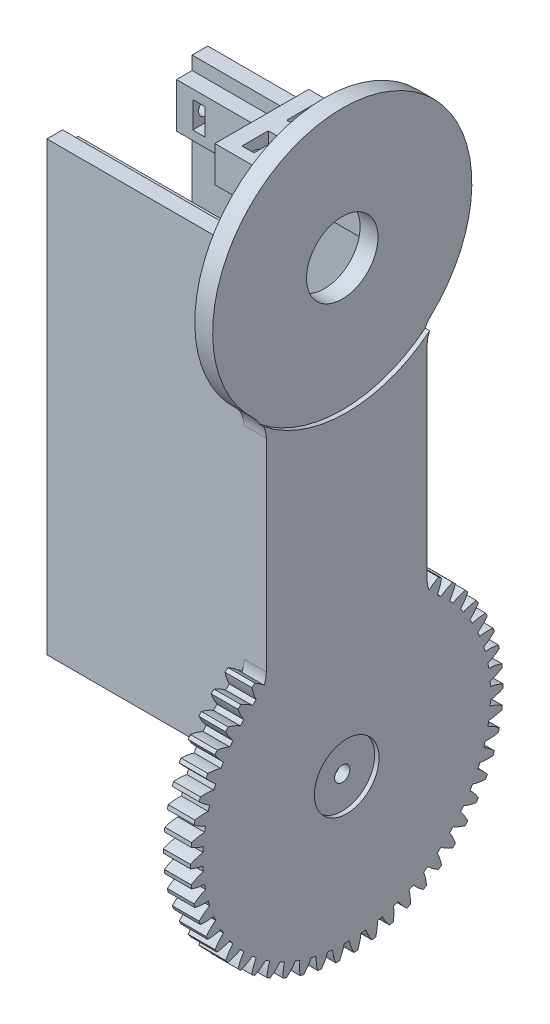
SolidWorks part; units mm, degrees
ref_plane "Front Plane" through (0, 0, 0) normal (0, 0, 1) x (1, 0, 0)
ref_plane "Top Plane" through (0, 0, 0) normal (0, 1, 0) x (1, 0, 0)
ref_plane "Right Plane" through (0, 0, 0) normal (1, 0, 0) x (0, 0, -1)
sketch "Sketch1" plane through (0, 0, 0) normal (1, 0, 0) x (0, 0, -1)
  line L0 (-32, 131.6872) -> (-32, 177.0245)
  line L1 (4, 177.0245) -> (4, 131.6872)
  arc A0 (6.1892, 127.0528) -> (-34.1892, 127.0528) centre (-14, 102.5) cw
  arc A1 (-34.1892, 127.0528) -> (-32, 131.6872) centre (-38, 131.6872) ccw
  arc A2 (-32, 177.0245) -> (-33.8857, 181.3917) centre (-38, 177.0245) ccw
  arc A3 (-33.8857, 181.3917) -> (5.8857, 181.3917) centre (-14, 202.5) cw
  arc A4 (5.8857, 181.3917) -> (4, 177.0245) centre (10, 177.0245) ccw
  arc A5 (4, 131.6872) -> (6.1892, 127.0528) centre (10, 131.6872) ccw
  circle A6 centre (-14, 202.5) radius 8
extrude "Plate A" add sketch "Sketch1" along normal blind 5 from offset 22.05
sketch "Sketch2" plane through (0, 0, 0) normal (1, 0, 0) x (0, 0, -1)
  arc A0 (20.9973, 102.0644) -> (20.9973, 102.9356) centre (-14, 102.5) ccw
  arc A1 (18.1607, 103.8131) -> (18.0957, 104.9294) centre (-14, 102.5) ccw
  arc A2 (20.8112, 106.1303) -> (20.7101, 106.9956) centre (-14, 102.5) ccw
  arc A3 (17.7908, 107.5378) -> (17.5966, 108.6391) centre (-14, 102.5) ccw
  arc A4 (20.1544, 110.1471) -> (19.9535, 110.9948) centre (-14, 102.5) ccw
  arc A5 (16.991, 111.1945) -> (16.6703, 112.2657) centre (-14, 102.5) ccw
  arc A6 (19.0357, 114.0605) -> (18.7377, 114.8791) centre (-14, 102.5) ccw
  arc A7 (15.7721, 114.7335) -> (15.3292, 115.7603) centre (-14, 102.5) ccw
  arc A8 (17.4702, 117.8175) -> (17.0792, 118.596) centre (-14, 102.5) ccw
  arc A9 (14.1505, 118.1071) -> (13.5914, 119.0755) centre (-14, 102.5) ccw
  arc A10 (15.4792, 121.3674) -> (15.0004, 122.0953) centre (-14, 102.5) ccw
  arc A11 (12.1483, 121.2697) -> (11.4806, 122.1666) centre (-14, 102.5) ccw
  arc A12 (13.0895, 124.6621) -> (12.5295, 125.3295) centre (-14, 102.5) ccw
  arc A13 (9.7925, 124.1784) -> (9.0251, 124.9917) centre (-14, 102.5) ccw
  arc A14 (10.3334, 127.6572) -> (9.6998, 128.255) centre (-14, 102.5) ccw
  arc A15 (7.1149, 126.794) -> (6.2583, 127.5127) centre (-14, 102.5) ccw
  arc A16 (7.2483, 130.312) -> (6.5495, 130.8323) centre (-14, 102.5) ccw
  arc A17 (4.1518, 129.081) -> (3.2175, 129.6954) centre (-14, 102.5) ccw
  arc A18 (3.8759, 132.5907) -> (3.1214, 133.0263) centre (-14, 102.5) ccw
  arc A19 (0.9432, 131.0085) -> (-0.0561, 131.5104) centre (-14, 102.5) ccw
  arc A20 (0.2617, 134.4625) -> (-0.5383, 134.8076) centre (-14, 102.5) ccw
  arc A21 (-2.4675, 132.5506) -> (-3.5183, 132.933) centre (-14, 102.5) ccw
  arc A22 (-3.5454, 135.9021) -> (-4.38, 136.152) centre (-14, 102.5) ccw
  arc A23 (-6.0341, 133.6862) -> (-7.1222, 133.9441) centre (-14, 102.5) ccw
  arc A24 (-7.4938, 136.89) -> (-8.3518, 137.0412) centre (-14, 102.5) ccw
  arc A25 (-9.7085, 134.4001) -> (-10.8191, 134.5299) centre (-14, 102.5) ccw
  arc A26 (-11.5302, 137.4128) -> (-12.3999, 137.4634) centre (-14, 102.5) ccw
  arc A27 (-13.4409, 134.6826) -> (-14.5591, 134.6826) centre (-14, 102.5) ccw
  arc A28 (-15.6001, 137.4634) -> (-16.4698, 137.4128) centre (-14, 102.5) ccw
  arc A29 (-17.1809, 134.5299) -> (-18.2915, 134.4001) centre (-14, 102.5) ccw
  arc A30 (-19.6482, 137.0412) -> (-20.5062, 136.89) centre (-14, 102.5) ccw
  arc A31 (-20.8778, 133.9441) -> (-21.9659, 133.6862) centre (-14, 102.5) ccw
  arc A32 (-23.62, 136.152) -> (-24.4546, 135.9021) centre (-14, 102.5) ccw
  arc A33 (-24.4817, 132.933) -> (-25.5325, 132.5506) centre (-14, 102.5) ccw
  arc A34 (-27.4617, 134.8076) -> (-28.2617, 134.4625) centre (-14, 102.5) ccw
  arc A35 (-27.9439, 131.5104) -> (-28.9432, 131.0085) centre (-14, 102.5) ccw
  arc A36 (-31.1214, 133.0263) -> (-31.8759, 132.5907) centre (-14, 102.5) ccw
  arc A37 (-31.2175, 129.6954) -> (-32.1518, 129.081) centre (-14, 102.5) ccw
  arc A38 (-34.5495, 130.8323) -> (-35.2483, 130.312) centre (-14, 102.5) ccw
  arc A39 (-34.2583, 127.5127) -> (-35.1149, 126.794) centre (-14, 102.5) ccw
  arc A40 (-37.6998, 128.255) -> (-38.3334, 127.6572) centre (-14, 102.5) ccw
  arc A41 (-37.0251, 124.9917) -> (-37.7925, 124.1784) centre (-14, 102.5) ccw
  arc A42 (-40.5295, 125.3295) -> (-41.0895, 124.6621) centre (-14, 102.5) ccw
  arc A43 (-39.4806, 122.1666) -> (-40.1483, 121.2697) centre (-14, 102.5) ccw
  arc A44 (-43.0004, 122.0953) -> (-43.4792, 121.3674) centre (-14, 102.5) ccw
  arc A45 (-41.5914, 119.0755) -> (-42.1505, 118.1071) centre (-14, 102.5) ccw
  arc A46 (-45.0792, 118.596) -> (-45.4702, 117.8175) centre (-14, 102.5) ccw
  arc A47 (-43.3292, 115.7603) -> (-43.7721, 114.7335) centre (-14, 102.5) ccw
  arc A48 (-46.7377, 114.8791) -> (-47.0357, 114.0605) centre (-14, 102.5) ccw
  arc A49 (-44.6703, 112.2657) -> (-44.991, 111.1945) centre (-14, 102.5) ccw
  arc A50 (-47.9535, 110.9948) -> (-48.1544, 110.1471) centre (-14, 102.5) ccw
  arc A51 (-45.5966, 108.6391) -> (-45.7908, 107.5378) centre (-14, 102.5) ccw
  arc A52 (-48.7101, 106.9956) -> (-48.8112, 106.1303) centre (-14, 102.5) ccw
  arc A53 (-46.0957, 104.9294) -> (-46.1607, 103.8131) centre (-14, 102.5) ccw
  arc A54 (-48.9973, 102.9356) -> (-48.9973, 102.0644) centre (-14, 102.5) ccw
  arc A55 (-46.1607, 101.1869) -> (-46.0957, 100.0706) centre (-14, 102.5) ccw
  arc A56 (-48.8112, 98.8697) -> (-48.7101, 98.0044) centre (-14, 102.5) ccw
  arc A57 (-45.7908, 97.4622) -> (-45.5966, 96.3609) centre (-14, 102.5) ccw
  arc A58 (-48.1544, 94.8529) -> (-47.9535, 94.0052) centre (-14, 102.5) ccw
  arc A59 (-44.991, 93.8055) -> (-44.6703, 92.7343) centre (-14, 102.5) ccw
  arc A60 (-47.0357, 90.9395) -> (-46.7377, 90.1209) centre (-14, 102.5) ccw
  arc A61 (-43.7721, 90.2665) -> (-43.3292, 89.2397) centre (-14, 102.5) ccw
  arc A62 (-45.4702, 87.1825) -> (-45.0792, 86.404) centre (-14, 102.5) ccw
  arc A63 (-42.1505, 86.8929) -> (-41.5914, 85.9245) centre (-14, 102.5) ccw
  arc A64 (-43.4792, 83.6326) -> (-43.0004, 82.9047) centre (-14, 102.5) ccw
  arc A65 (-40.1483, 83.7303) -> (-39.4806, 82.8334) centre (-14, 102.5) ccw
  arc A66 (-41.0895, 80.3379) -> (-40.5295, 79.6705) centre (-14, 102.5) ccw
  arc A67 (-37.7925, 80.8216) -> (-37.0251, 80.0083) centre (-14, 102.5) ccw
  arc A68 (-38.3334, 77.3428) -> (-37.6998, 76.745) centre (-14, 102.5) ccw
  arc A69 (-35.1149, 78.206) -> (-34.2583, 77.4873) centre (-14, 102.5) ccw
  arc A70 (-35.2483, 74.688) -> (-34.5495, 74.1677) centre (-14, 102.5) ccw
  arc A71 (-32.1518, 75.919) -> (-31.2175, 75.3046) centre (-14, 102.5) ccw
  arc A72 (-31.8759, 72.4093) -> (-31.1214, 71.9737) centre (-14, 102.5) ccw
  arc A73 (-28.9432, 73.9915) -> (-27.9439, 73.4896) centre (-14, 102.5) ccw
  arc A74 (-28.2617, 70.5375) -> (-27.4617, 70.1924) centre (-14, 102.5) ccw
  arc A75 (-25.5325, 72.4494) -> (-24.4817, 72.067) centre (-14, 102.5) ccw
  arc A76 (-24.4546, 69.0979) -> (-23.62, 68.848) centre (-14, 102.5) ccw
  arc A77 (-21.9659, 71.3138) -> (-20.8778, 71.0559) centre (-14, 102.5) ccw
  arc A78 (-20.5062, 68.11) -> (-19.6482, 67.9588) centre (-14, 102.5) ccw
  arc A79 (-18.2915, 70.5999) -> (-17.1809, 70.4701) centre (-14, 102.5) ccw
  arc A80 (-16.4698, 67.5872) -> (-15.6001, 67.5366) centre (-14, 102.5) ccw
  arc A81 (-14.5591, 70.3174) -> (-13.4409, 70.3174) centre (-14, 102.5) ccw
  arc A82 (-12.3999, 67.5366) -> (-11.5302, 67.5872) centre (-14, 102.5) ccw
  arc A83 (-10.8191, 70.4701) -> (-9.7085, 70.5999) centre (-14, 102.5) ccw
  arc A84 (-8.3518, 67.9588) -> (-7.4938, 68.11) centre (-14, 102.5) ccw
  arc A85 (-7.1222, 71.0559) -> (-6.0341, 71.3138) centre (-14, 102.5) ccw
  arc A86 (-4.38, 68.848) -> (-3.5454, 69.0979) centre (-14, 102.5) ccw
  arc A87 (-3.5183, 72.067) -> (-2.4675, 72.4494) centre (-14, 102.5) ccw
  arc A88 (-0.5383, 70.1924) -> (0.2617, 70.5375) centre (-14, 102.5) ccw
  arc A89 (-0.0561, 73.4896) -> (0.9432, 73.9915) centre (-14, 102.5) ccw
  arc A90 (3.1214, 71.9737) -> (3.8759, 72.4093) centre (-14, 102.5) ccw
  arc A91 (3.2175, 75.3046) -> (4.1518, 75.919) centre (-14, 102.5) ccw
  arc A92 (6.5495, 74.1677) -> (7.2483, 74.688) centre (-14, 102.5) ccw
  arc A93 (6.2583, 77.4873) -> (7.1149, 78.206) centre (-14, 102.5) ccw
  arc A94 (9.6998, 76.745) -> (10.3334, 77.3428) centre (-14, 102.5) ccw
  arc A95 (9.0251, 80.0083) -> (9.7925, 80.8216) centre (-14, 102.5) ccw
  arc A96 (12.5295, 79.6705) -> (13.0895, 80.3379) centre (-14, 102.5) ccw
  arc A97 (11.4806, 82.8334) -> (12.1483, 83.7303) centre (-14, 102.5) ccw
  arc A98 (15.0004, 82.9047) -> (15.4792, 83.6326) centre (-14, 102.5) ccw
  arc A99 (13.5914, 85.9245) -> (14.1505, 86.8929) centre (-14, 102.5) ccw
  arc A100 (17.0792, 86.404) -> (17.4702, 87.1825) centre (-14, 102.5) ccw
  arc A101 (15.3292, 89.2397) -> (15.7721, 90.2665) centre (-14, 102.5) ccw
  arc A102 (18.7377, 90.1209) -> (19.0357, 90.9395) centre (-14, 102.5) ccw
  arc A103 (16.6703, 92.7343) -> (16.991, 93.8055) centre (-14, 102.5) ccw
  arc A104 (19.9535, 94.0052) -> (20.1544, 94.8529) centre (-14, 102.5) ccw
  arc A105 (17.5966, 96.3609) -> (17.7908, 97.4622) centre (-14, 102.5) ccw
  arc A106 (20.7101, 98.0044) -> (20.8112, 98.8697) centre (-14, 102.5) ccw
  arc A107 (18.0957, 100.0706) -> (18.1607, 101.1869) centre (-14, 102.5) ccw
  spline S0 degree 3 poles (18.1607, 101.1869) (18.3503, 101.2175) (18.7327, 101.2791) (19.3001, 101.4275) (19.868, 101.6076) (20.4361, 101.819) (20.8092, 101.9822) (20.9973, 102.0644) knots 0 0 0 0 0.193275 0.389922 0.589928 0.793288 1 1 1 1
  spline S1 degree 3 poles (20.9973, 102.9356) (20.8092, 103.0178) (20.4361, 103.181) (19.868, 103.3924) (19.3001, 103.5725) (18.7327, 103.7209) (18.3503, 103.7825) (18.1607, 103.8131) knots 0 0 0 0 0.206712 0.410072 0.610078 0.806725 1 1 1 1
  spline S2 degree 3 poles (18.0957, 104.9294) (18.2804, 104.9818) (18.6531, 105.0874) (19.1994, 105.3007) (19.7426, 105.5455) (20.2823, 105.8214) (20.634, 106.0268) (20.8112, 106.1303) knots 0 0 0 0 0.193275 0.389922 0.589928 0.793288 1 1 1 1
  spline S3 degree 3 poles (20.7101, 106.9956) (20.5137, 107.0554) (20.1242, 107.1742) (19.5354, 107.3182) (18.9504, 107.4311) (18.3696, 107.5127) (17.9826, 107.5295) (17.7908, 107.5378) knots 0 0 0 0 0.206712 0.410072 0.610078 0.806725 1 1 1 1
  spline S4 degree 3 poles (17.5966, 108.6391) (17.774, 108.7125) (18.1319, 108.8607) (18.6498, 109.136) (19.1609, 109.4422) (19.6649, 109.7789) (19.9904, 110.0237) (20.1544, 110.1471) knots 0 0 0 0 0.193275 0.389922 0.589928 0.793288 1 1 1 1
  spline S5 degree 3 poles (19.9535, 110.9948) (19.7515, 111.0314) (19.3508, 111.1042) (18.7493, 111.1788) (18.1551, 111.2231) (17.5688, 111.2366) (17.1825, 111.2084) (16.991, 111.1945) knots 0 0 0 0 0.206712 0.410072 0.610078 0.806725 1 1 1 1
  spline S6 degree 3 poles (16.6703, 112.2657) (16.838, 112.3592) (17.1762, 112.548) (17.6586, 112.8815) (18.1308, 113.245) (18.5923, 113.6379) (18.8871, 113.9188) (19.0357, 114.0605) knots 0 0 0 0 0.193275 0.389922 0.589928 0.793288 1 1 1 1
  spline S7 degree 3 poles (18.7377, 114.8791) (18.5328, 114.8921) (18.1264, 114.9178) (17.5203, 114.9221) (16.925, 114.8971) (16.3411, 114.8425) (15.9606, 114.7696) (15.7721, 114.7335) knots 0 0 0 0 0.206712 0.410072 0.610078 0.806725 1 1 1 1
  spline S8 degree 3 poles (15.3292, 115.7603) (15.4848, 115.8727) (15.7989, 116.0994) (16.2394, 116.4866) (16.6661, 116.9025) (17.0789, 117.3463) (17.3391, 117.6596) (17.4702, 117.8175) knots 0 0 0 0 0.193275 0.389922 0.589928 0.793288 1 1 1 1
  spline S9 degree 3 poles (17.0792, 118.596) (16.8742, 118.5851) (16.4676, 118.5635) (15.8651, 118.4974) (15.2767, 118.4034) (14.7031, 118.2814) (14.3336, 118.1649) (14.1505, 118.1071) knots 0 0 0 0 0.206712 0.410072 0.610078 0.806725 1 1 1 1
  spline S10 degree 3 poles (13.5914, 119.0755) (13.733, 119.2052) (14.0186, 119.4669) (14.4111, 119.9026) (14.7867, 120.3652) (15.1452, 120.854) (15.3672, 121.1953) (15.4792, 121.3674) knots 0 0 0 0 0.193275 0.389922 0.589928 0.793288 1 1 1 1
  spline S11 degree 3 poles (15.0004, 122.0953) (14.7981, 122.0606) (14.3967, 121.9919) (13.806, 121.8564) (13.2325, 121.6947) (12.6769, 121.5069) (12.3235, 121.3483) (12.1483, 121.2697) knots 0 0 0 0 0.206712 0.410072 0.610078 0.806725 1 1 1 1
  spline S12 degree 3 poles (11.4806, 122.1666) (11.6061, 122.3119) (11.8594, 122.6049) (12.1987, 123.0833) (12.518, 123.5864) (12.8173, 124.1134) (12.9983, 124.4782) (13.0895, 124.6621) knots 0 0 0 0 0.193275 0.389922 0.589928 0.793288 1 1 1 1
  spline S13 degree 3 poles (12.5295, 125.3295) (12.3325, 125.2716) (11.9419, 125.1568) (11.3708, 124.9536) (10.82, 124.7264) (10.2899, 124.4754) (9.9573, 124.2768) (9.7925, 124.1784) knots 0 0 0 0 0.206712 0.410072 0.610078 0.806725 1 1 1 1
  spline S14 degree 3 poles (9.0251, 124.9917) (9.133, 125.1506) (9.3506, 125.4711) (9.632, 125.9856) (9.8908, 126.5223) (10.1268, 127.0806) (10.2642, 127.4639) (10.3334, 127.6572) knots 0 0 0 0 0.193275 0.389922 0.589928 0.793288 1 1 1 1
  spline S15 degree 3 poles (9.6998, 128.255) (9.5109, 128.1747) (9.1361, 128.0153) (8.5926, 127.7471) (8.0718, 127.4576) (7.5745, 127.1467) (7.2672, 126.9109) (7.1149, 126.794) knots 0 0 0 0 0.206712 0.410072 0.610078 0.806725 1 1 1 1
  spline S16 degree 3 poles (6.2583, 127.5127) (6.347, 127.683) (6.5259, 128.0266) (6.7457, 128.5703) (6.9404, 129.1334) (7.1101, 129.7153) (7.202, 130.112) (7.2483, 130.312) knots 0 0 0 0 0.193275 0.389922 0.589928 0.793288 1 1 1 1
  spline S17 degree 3 poles (6.5495, 130.8323) (6.3712, 130.7305) (6.0176, 130.5287) (5.5088, 130.1992) (5.0252, 129.8512) (4.5673, 129.4847) (4.2895, 129.2148) (4.1518, 129.081) knots 0 0 0 0 0.206712 0.410072 0.610078 0.806725 1 1 1 1
  spline S18 degree 3 poles (3.2175, 129.6954) (3.2858, 129.8749) (3.4237, 130.2369) (3.5788, 130.8025) (3.7069, 131.3844) (3.8078, 131.982) (3.8531, 132.3867) (3.8759, 132.5907) knots 0 0 0 0 0.193275 0.389922 0.589928 0.793288 1 1 1 1
  spline S19 degree 3 poles (3.1214, 133.0263) (2.9561, 132.9046) (2.6283, 132.6631) (2.1612, 132.2768) (1.7212, 131.8749) (1.309, 131.4578) (1.0644, 131.1574) (0.9432, 131.0085) knots 0 0 0 0 0.206712 0.410072 0.610078 0.806725 1 1 1 1
  spline S20 degree 3 poles (-0.0561, 131.5104) (-0.0091, 131.6965) (0.0858, 132.0721) (0.1743, 132.6519) (0.2339, 133.2447) (0.2648, 133.8501) (0.2627, 134.2573) (0.2617, 134.4625) knots 0 0 0 0 0.193275 0.389922 0.589928 0.793288 1 1 1 1
  spline S21 degree 3 poles (-0.5383, 134.8076) (-0.6883, 134.6675) (-0.9859, 134.3895) (-1.405, 133.9516) (-1.7953, 133.5014) (-2.1563, 133.0392) (-2.3644, 132.7125) (-2.4675, 132.5506) knots 0 0 0 0 0.206712 0.410072 0.610078 0.806725 1 1 1 1
  spline S22 degree 3 poles (-3.5183, 132.933) (-3.4932, 133.1234) (-3.4426, 133.5074) (-3.422, 134.0935) (-3.4316, 134.6893) (-3.4712, 135.2941) (-3.5205, 135.6983) (-3.5454, 135.9021) knots 0 0 0 0 0.193275 0.389922 0.589928 0.793288 1 1 1 1
  spline S23 degree 3 poles (-4.38, 136.152) (-4.5127, 135.9954) (-4.776, 135.6848) (-5.1414, 135.2012) (-5.4769, 134.7087) (-5.7818, 134.2077) (-5.9505, 133.859) (-6.0341, 133.6862) knots 0 0 0 0 0.206712 0.410072 0.610078 0.806725 1 1 1 1
  spline S24 degree 3 poles (-7.1222, 133.9441) (-7.1194, 134.1361) (-7.1137, 134.5234) (-7.1613, 135.1079) (-7.24, 135.6986) (-7.3496, 136.2947) (-7.4455, 136.6905) (-7.4938, 136.89) knots 0 0 0 0 0.193275 0.389922 0.589928 0.793288 1 1 1 1
  spline S25 degree 3 poles (-8.3518, 137.0412) (-8.4654, 136.8703) (-8.6909, 136.5312) (-8.9977, 136.0085) (-9.2737, 135.4804) (-9.5184, 134.9474) (-9.6455, 134.5815) (-9.7085, 134.4001) knots 0 0 0 0 0.206712 0.410072 0.610078 0.806725 1 1 1 1
  spline S26 degree 3 poles (-10.8191, 134.5299) (-10.8386, 134.721) (-10.8779, 135.1063) (-10.9931, 135.6814) (-11.1399, 136.2589) (-11.3179, 136.8383) (-11.4591, 137.2202) (-11.5302, 137.4128) knots 0 0 0 0 0.193275 0.389922 0.589928 0.793288 1 1 1 1
  spline S27 degree 3 poles (-12.3999, 137.4634) (-12.493, 137.2804) (-12.6776, 136.9175) (-12.9216, 136.3626) (-13.1344, 135.8061) (-13.3156, 135.2483) (-13.3994, 134.8701) (-13.4409, 134.6826) knots 0 0 0 0 0.206712 0.410072 0.610078 0.806725 1 1 1 1
  spline S28 degree 3 poles (-14.5591, 134.6826) (-14.6006, 134.8701) (-14.6844, 135.2483) (-14.8656, 135.8061) (-15.0784, 136.3626) (-15.3224, 136.9175) (-15.507, 137.2804) (-15.6001, 137.4634) knots 0 0 0 0 0.193275 0.389922 0.589928 0.793288 1 1 1 1
  spline S29 degree 3 poles (-16.4698, 137.4128) (-16.5409, 137.2202) (-16.6821, 136.8383) (-16.8601, 136.2589) (-17.0069, 135.6814) (-17.1221, 135.1063) (-17.1614, 134.721) (-17.1809, 134.5299) knots 0 0 0 0 0.206712 0.410072 0.610078 0.806725 1 1 1 1
  spline S30 degree 3 poles (-18.2915, 134.4001) (-18.3545, 134.5815) (-18.4816, 134.9474) (-18.7263, 135.4804) (-19.0023, 136.0085) (-19.3091, 136.5312) (-19.5346, 136.8703) (-19.6482, 137.0412) knots 0 0 0 0 0.193275 0.389922 0.589928 0.793288 1 1 1 1
  spline S31 degree 3 poles (-20.5062, 136.89) (-20.5545, 136.6905) (-20.6504, 136.2947) (-20.76, 135.6986) (-20.8387, 135.1079) (-20.8863, 134.5234) (-20.8806, 134.1361) (-20.8778, 133.9441) knots 0 0 0 0 0.206712 0.410072 0.610078 0.806725 1 1 1 1
  spline S32 degree 3 poles (-21.9659, 133.6862) (-22.0495, 133.859) (-22.2182, 134.2077) (-22.5231, 134.7087) (-22.8586, 135.2012) (-23.224, 135.6848) (-23.4873, 135.9954) (-23.62, 136.152) knots 0 0 0 0 0.193275 0.389922 0.589928 0.793288 1 1 1 1
  spline S33 degree 3 poles (-24.4546, 135.9021) (-24.4795, 135.6983) (-24.5288, 135.2941) (-24.5684, 134.6893) (-24.578, 134.0935) (-24.5574, 133.5074) (-24.5068, 133.1234) (-24.4817, 132.933) knots 0 0 0 0 0.206712 0.410072 0.610078 0.806725 1 1 1 1
  spline S34 degree 3 poles (-25.5325, 132.5506) (-25.6356, 132.7125) (-25.8437, 133.0392) (-26.2047, 133.5014) (-26.595, 133.9516) (-27.0141, 134.3895) (-27.3117, 134.6675) (-27.4617, 134.8076) knots 0 0 0 0 0.193275 0.389922 0.589928 0.793288 1 1 1 1
  spline S35 degree 3 poles (-28.2617, 134.4625) (-28.2627, 134.2573) (-28.2648, 133.8501) (-28.2339, 133.2447) (-28.1743, 132.6519) (-28.0858, 132.0721) (-27.9909, 131.6965) (-27.9439, 131.5104) knots 0 0 0 0 0.206712 0.410072 0.610078 0.806725 1 1 1 1
  spline S36 degree 3 poles (-28.9432, 131.0085) (-29.0644, 131.1574) (-29.309, 131.4578) (-29.7212, 131.8749) (-30.1612, 132.2768) (-30.6283, 132.6631) (-30.9561, 132.9046) (-31.1214, 133.0263) knots 0 0 0 0 0.193275 0.389922 0.589928 0.793288 1 1 1 1
  spline S37 degree 3 poles (-31.8759, 132.5907) (-31.8531, 132.3867) (-31.8078, 131.982) (-31.7069, 131.3844) (-31.5788, 130.8025) (-31.4237, 130.2369) (-31.2858, 129.8749) (-31.2175, 129.6954) knots 0 0 0 0 0.206712 0.410072 0.610078 0.806725 1 1 1 1
  spline S38 degree 3 poles (-32.1518, 129.081) (-32.2895, 129.2148) (-32.5673, 129.4847) (-33.0252, 129.8512) (-33.5088, 130.1992) (-34.0176, 130.5287) (-34.3712, 130.7305) (-34.5495, 130.8323) knots 0 0 0 0 0.193275 0.389922 0.589928 0.793288 1 1 1 1
  spline S39 degree 3 poles (-35.2483, 130.312) (-35.202, 130.112) (-35.1101, 129.7153) (-34.9404, 129.1334) (-34.7457, 128.5703) (-34.5259, 128.0266) (-34.347, 127.683) (-34.2583, 127.5127) knots 0 0 0 0 0.206712 0.410072 0.610078 0.806725 1 1 1 1
  spline S40 degree 3 poles (-35.1149, 126.794) (-35.2672, 126.9109) (-35.5745, 127.1467) (-36.0718, 127.4576) (-36.5926, 127.7471) (-37.1361, 128.0153) (-37.5109, 128.1747) (-37.6998, 128.255) knots 0 0 0 0 0.193275 0.389922 0.589928 0.793288 1 1 1 1
  spline S41 degree 3 poles (-38.3334, 127.6572) (-38.2642, 127.4639) (-38.1268, 127.0806) (-37.8908, 126.5223) (-37.632, 125.9856) (-37.3506, 125.4711) (-37.133, 125.1506) (-37.0251, 124.9917) knots 0 0 0 0 0.206712 0.410072 0.610078 0.806725 1 1 1 1
  spline S42 degree 3 poles (-37.7925, 124.1784) (-37.9573, 124.2768) (-38.2899, 124.4754) (-38.82, 124.7264) (-39.3708, 124.9536) (-39.9419, 125.1568) (-40.3325, 125.2716) (-40.5295, 125.3295) knots 0 0 0 0 0.193275 0.389922 0.589928 0.793288 1 1 1 1
  spline S43 degree 3 poles (-41.0895, 124.6621) (-40.9983, 124.4782) (-40.8173, 124.1134) (-40.518, 123.5864) (-40.1987, 123.0833) (-39.8594, 122.6049) (-39.6061, 122.3119) (-39.4806, 122.1666) knots 0 0 0 0 0.206712 0.410072 0.610078 0.806725 1 1 1 1
  spline S44 degree 3 poles (-40.1483, 121.2697) (-40.3235, 121.3483) (-40.6769, 121.5069) (-41.2325, 121.6947) (-41.806, 121.8564) (-42.3967, 121.9919) (-42.7981, 122.0606) (-43.0004, 122.0953) knots 0 0 0 0 0.193275 0.389922 0.589928 0.793288 1 1 1 1
  spline S45 degree 3 poles (-43.4792, 121.3674) (-43.3672, 121.1953) (-43.1452, 120.854) (-42.7867, 120.3652) (-42.4111, 119.9026) (-42.0186, 119.4669) (-41.733, 119.2052) (-41.5914, 119.0755) knots 0 0 0 0 0.206712 0.410072 0.610078 0.806725 1 1 1 1
  spline S46 degree 3 poles (-42.1505, 118.1071) (-42.3336, 118.1649) (-42.7031, 118.2814) (-43.2767, 118.4034) (-43.8651, 118.4974) (-44.4676, 118.5635) (-44.8742, 118.5851) (-45.0792, 118.596) knots 0 0 0 0 0.193275 0.389922 0.589928 0.793288 1 1 1 1
  spline S47 degree 3 poles (-45.4702, 117.8175) (-45.3391, 117.6596) (-45.0789, 117.3463) (-44.6661, 116.9025) (-44.2394, 116.4866) (-43.7989, 116.0994) (-43.4848, 115.8727) (-43.3292, 115.7603) knots 0 0 0 0 0.206712 0.410072 0.610078 0.806725 1 1 1 1
  spline S48 degree 3 poles (-43.7721, 114.7335) (-43.9606, 114.7696) (-44.3411, 114.8425) (-44.925, 114.8971) (-45.5203, 114.9221) (-46.1264, 114.9178) (-46.5328, 114.8921) (-46.7377, 114.8791) knots 0 0 0 0 0.193275 0.389922 0.589928 0.793288 1 1 1 1
  spline S49 degree 3 poles (-47.0357, 114.0605) (-46.8871, 113.9188) (-46.5923, 113.6379) (-46.1308, 113.245) (-45.6586, 112.8815) (-45.1762, 112.548) (-44.838, 112.3592) (-44.6703, 112.2657) knots 0 0 0 0 0.206712 0.410072 0.610078 0.806725 1 1 1 1
  spline S50 degree 3 poles (-44.991, 111.1945) (-45.1825, 111.2084) (-45.5688, 111.2366) (-46.1551, 111.2231) (-46.7493, 111.1788) (-47.3508, 111.1042) (-47.7515, 111.0314) (-47.9535, 110.9948) knots 0 0 0 0 0.193275 0.389922 0.589928 0.793288 1 1 1 1
  spline S51 degree 3 poles (-48.1544, 110.1471) (-47.9904, 110.0237) (-47.6649, 109.7789) (-47.1609, 109.4422) (-46.6498, 109.136) (-46.1319, 108.8607) (-45.774, 108.7125) (-45.5966, 108.6391) knots 0 0 0 0 0.206712 0.410072 0.610078 0.806725 1 1 1 1
  spline S52 degree 3 poles (-45.7908, 107.5378) (-45.9826, 107.5295) (-46.3696, 107.5127) (-46.9504, 107.4311) (-47.5354, 107.3182) (-48.1242, 107.1742) (-48.5137, 107.0554) (-48.7101, 106.9956) knots 0 0 0 0 0.193275 0.389922 0.589928 0.793288 1 1 1 1
  spline S53 degree 3 poles (-48.8112, 106.1303) (-48.634, 106.0268) (-48.2823, 105.8214) (-47.7426, 105.5455) (-47.1994, 105.3007) (-46.6531, 105.0874) (-46.2804, 104.9818) (-46.0957, 104.9294) knots 0 0 0 0 0.206712 0.410072 0.610078 0.806725 1 1 1 1
  spline S54 degree 3 poles (-46.1607, 103.8131) (-46.3503, 103.7825) (-46.7327, 103.7209) (-47.3001, 103.5725) (-47.868, 103.3924) (-48.4361, 103.181) (-48.8092, 103.0178) (-48.9973, 102.9356) knots 0 0 0 0 0.193275 0.389922 0.589928 0.793288 1 1 1 1
  spline S55 degree 3 poles (-48.9973, 102.0644) (-48.8092, 101.9822) (-48.4361, 101.819) (-47.868, 101.6076) (-47.3001, 101.4275) (-46.7327, 101.2791) (-46.3503, 101.2175) (-46.1607, 101.1869) knots 0 0 0 0 0.206712 0.410072 0.610078 0.806725 1 1 1 1
  spline S56 degree 3 poles (-46.0957, 100.0706) (-46.2804, 100.0182) (-46.6531, 99.9126) (-47.1994, 99.6993) (-47.7426, 99.4545) (-48.2823, 99.1786) (-48.634, 98.9732) (-48.8112, 98.8697) knots 0 0 0 0 0.193275 0.389922 0.589928 0.793288 1 1 1 1
  spline S57 degree 3 poles (-48.7101, 98.0044) (-48.5137, 97.9446) (-48.1242, 97.8258) (-47.5354, 97.6818) (-46.9504, 97.5689) (-46.3696, 97.4873) (-45.9826, 97.4705) (-45.7908, 97.4622) knots 0 0 0 0 0.206712 0.410072 0.610078 0.806725 1 1 1 1
  spline S58 degree 3 poles (-45.5966, 96.3609) (-45.774, 96.2875) (-46.1319, 96.1393) (-46.6498, 95.864) (-47.1609, 95.5578) (-47.6649, 95.2211) (-47.9904, 94.9763) (-48.1544, 94.8529) knots 0 0 0 0 0.193275 0.389922 0.589928 0.793288 1 1 1 1
  spline S59 degree 3 poles (-47.9535, 94.0052) (-47.7515, 93.9686) (-47.3508, 93.8958) (-46.7493, 93.8212) (-46.1551, 93.7769) (-45.5688, 93.7634) (-45.1825, 93.7916) (-44.991, 93.8055) knots 0 0 0 0 0.206712 0.410072 0.610078 0.806725 1 1 1 1
  spline S60 degree 3 poles (-44.6703, 92.7343) (-44.838, 92.6408) (-45.1762, 92.452) (-45.6586, 92.1185) (-46.1308, 91.755) (-46.5923, 91.3621) (-46.8871, 91.0812) (-47.0357, 90.9395) knots 0 0 0 0 0.193275 0.389922 0.589928 0.793288 1 1 1 1
  spline S61 degree 3 poles (-46.7377, 90.1209) (-46.5328, 90.1079) (-46.1264, 90.0822) (-45.5203, 90.0779) (-44.925, 90.1029) (-44.3411, 90.1575) (-43.9606, 90.2304) (-43.7721, 90.2665) knots 0 0 0 0 0.206712 0.410072 0.610078 0.806725 1 1 1 1
  spline S62 degree 3 poles (-43.3292, 89.2397) (-43.4848, 89.1273) (-43.7989, 88.9006) (-44.2394, 88.5134) (-44.6661, 88.0975) (-45.0789, 87.6537) (-45.3391, 87.3404) (-45.4702, 87.1825) knots 0 0 0 0 0.193275 0.389922 0.589928 0.793288 1 1 1 1
  spline S63 degree 3 poles (-45.0792, 86.404) (-44.8742, 86.4149) (-44.4676, 86.4365) (-43.8651, 86.5026) (-43.2767, 86.5966) (-42.7031, 86.7186) (-42.3336, 86.8351) (-42.1505, 86.8929) knots 0 0 0 0 0.206712 0.410072 0.610078 0.806725 1 1 1 1
  spline S64 degree 3 poles (-41.5914, 85.9245) (-41.733, 85.7948) (-42.0186, 85.5331) (-42.4111, 85.0974) (-42.7867, 84.6348) (-43.1452, 84.146) (-43.3672, 83.8047) (-43.4792, 83.6326) knots 0 0 0 0 0.193275 0.389922 0.589928 0.793288 1 1 1 1
  spline S65 degree 3 poles (-43.0004, 82.9047) (-42.7981, 82.9394) (-42.3967, 83.0081) (-41.806, 83.1436) (-41.2325, 83.3053) (-40.6769, 83.4931) (-40.3235, 83.6517) (-40.1483, 83.7303) knots 0 0 0 0 0.206712 0.410072 0.610078 0.806725 1 1 1 1
  spline S66 degree 3 poles (-39.4806, 82.8334) (-39.6061, 82.6881) (-39.8594, 82.3951) (-40.1987, 81.9167) (-40.518, 81.4136) (-40.8173, 80.8866) (-40.9983, 80.5218) (-41.0895, 80.3379) knots 0 0 0 0 0.193275 0.389922 0.589928 0.793288 1 1 1 1
  spline S67 degree 3 poles (-40.5295, 79.6705) (-40.3325, 79.7284) (-39.9419, 79.8432) (-39.3708, 80.0464) (-38.82, 80.2736) (-38.2899, 80.5246) (-37.9573, 80.7232) (-37.7925, 80.8216) knots 0 0 0 0 0.206712 0.410072 0.610078 0.806725 1 1 1 1
  spline S68 degree 3 poles (-37.0251, 80.0083) (-37.133, 79.8494) (-37.3506, 79.5289) (-37.632, 79.0144) (-37.8908, 78.4777) (-38.1268, 77.9194) (-38.2642, 77.5361) (-38.3334, 77.3428) knots 0 0 0 0 0.193275 0.389922 0.589928 0.793288 1 1 1 1
  spline S69 degree 3 poles (-37.6998, 76.745) (-37.5109, 76.8253) (-37.1361, 76.9847) (-36.5926, 77.2529) (-36.0718, 77.5424) (-35.5745, 77.8533) (-35.2672, 78.0891) (-35.1149, 78.206) knots 0 0 0 0 0.206712 0.410072 0.610078 0.806725 1 1 1 1
  spline S70 degree 3 poles (-34.2583, 77.4873) (-34.347, 77.317) (-34.5259, 76.9734) (-34.7457, 76.4297) (-34.9404, 75.8666) (-35.1101, 75.2847) (-35.202, 74.888) (-35.2483, 74.688) knots 0 0 0 0 0.193275 0.389922 0.589928 0.793288 1 1 1 1
  spline S71 degree 3 poles (-34.5495, 74.1677) (-34.3712, 74.2695) (-34.0176, 74.4713) (-33.5088, 74.8008) (-33.0252, 75.1488) (-32.5673, 75.5153) (-32.2895, 75.7852) (-32.1518, 75.919) knots 0 0 0 0 0.206712 0.410072 0.610078 0.806725 1 1 1 1
  spline S72 degree 3 poles (-31.2175, 75.3046) (-31.2858, 75.1251) (-31.4237, 74.7631) (-31.5788, 74.1975) (-31.7069, 73.6156) (-31.8078, 73.018) (-31.8531, 72.6133) (-31.8759, 72.4093) knots 0 0 0 0 0.193275 0.389922 0.589928 0.793288 1 1 1 1
  spline S73 degree 3 poles (-31.1214, 71.9737) (-30.9561, 72.0954) (-30.6283, 72.3369) (-30.1612, 72.7232) (-29.7212, 73.1251) (-29.309, 73.5422) (-29.0644, 73.8426) (-28.9432, 73.9915) knots 0 0 0 0 0.206712 0.410072 0.610078 0.806725 1 1 1 1
  spline S74 degree 3 poles (-27.9439, 73.4896) (-27.9909, 73.3035) (-28.0858, 72.9279) (-28.1743, 72.3481) (-28.2339, 71.7553) (-28.2648, 71.1499) (-28.2627, 70.7427) (-28.2617, 70.5375) knots 0 0 0 0 0.193275 0.389922 0.589928 0.793288 1 1 1 1
  spline S75 degree 3 poles (-27.4617, 70.1924) (-27.3117, 70.3325) (-27.0141, 70.6105) (-26.595, 71.0484) (-26.2047, 71.4986) (-25.8437, 71.9608) (-25.6356, 72.2875) (-25.5325, 72.4494) knots 0 0 0 0 0.206712 0.410072 0.610078 0.806725 1 1 1 1
  spline S76 degree 3 poles (-24.4817, 72.067) (-24.5068, 71.8766) (-24.5574, 71.4926) (-24.578, 70.9065) (-24.5684, 70.3107) (-24.5288, 69.7059) (-24.4795, 69.3017) (-24.4546, 69.0979) knots 0 0 0 0 0.193275 0.389922 0.589928 0.793288 1 1 1 1
  spline S77 degree 3 poles (-23.62, 68.848) (-23.4873, 69.0046) (-23.224, 69.3152) (-22.8586, 69.7988) (-22.5231, 70.2913) (-22.2182, 70.7923) (-22.0495, 71.141) (-21.9659, 71.3138) knots 0 0 0 0 0.206712 0.410072 0.610078 0.806725 1 1 1 1
  spline S78 degree 3 poles (-20.8778, 71.0559) (-20.8806, 70.8639) (-20.8863, 70.4766) (-20.8387, 69.8921) (-20.76, 69.3014) (-20.6504, 68.7053) (-20.5545, 68.3095) (-20.5062, 68.11) knots 0 0 0 0 0.193275 0.389922 0.589928 0.793288 1 1 1 1
  spline S79 degree 3 poles (-19.6482, 67.9588) (-19.5346, 68.1297) (-19.3091, 68.4688) (-19.0023, 68.9915) (-18.7263, 69.5196) (-18.4816, 70.0526) (-18.3545, 70.4185) (-18.2915, 70.5999) knots 0 0 0 0 0.206712 0.410072 0.610078 0.806725 1 1 1 1
  spline S80 degree 3 poles (-17.1809, 70.4701) (-17.1614, 70.279) (-17.1221, 69.8937) (-17.0069, 69.3186) (-16.8601, 68.7411) (-16.6821, 68.1617) (-16.5409, 67.7798) (-16.4698, 67.5872) knots 0 0 0 0 0.193275 0.389922 0.589928 0.793288 1 1 1 1
  spline S81 degree 3 poles (-15.6001, 67.5366) (-15.507, 67.7196) (-15.3224, 68.0825) (-15.0784, 68.6374) (-14.8656, 69.1939) (-14.6844, 69.7517) (-14.6006, 70.1299) (-14.5591, 70.3174) knots 0 0 0 0 0.206712 0.410072 0.610078 0.806725 1 1 1 1
  spline S82 degree 3 poles (-13.4409, 70.3174) (-13.3994, 70.1299) (-13.3156, 69.7517) (-13.1344, 69.1939) (-12.9216, 68.6374) (-12.6776, 68.0825) (-12.493, 67.7196) (-12.3999, 67.5366) knots 0 0 0 0 0.193275 0.389922 0.589928 0.793288 1 1 1 1
  spline S83 degree 3 poles (-11.5302, 67.5872) (-11.4591, 67.7798) (-11.3179, 68.1617) (-11.1399, 68.7411) (-10.9931, 69.3186) (-10.8779, 69.8937) (-10.8386, 70.279) (-10.8191, 70.4701) knots 0 0 0 0 0.206712 0.410072 0.610078 0.806725 1 1 1 1
  spline S84 degree 3 poles (-9.7085, 70.5999) (-9.6455, 70.4185) (-9.5184, 70.0526) (-9.2737, 69.5196) (-8.9977, 68.9915) (-8.6909, 68.4688) (-8.4654, 68.1297) (-8.3518, 67.9588) knots 0 0 0 0 0.193275 0.389922 0.589928 0.793288 1 1 1 1
  spline S85 degree 3 poles (-7.4938, 68.11) (-7.4455, 68.3095) (-7.3496, 68.7053) (-7.24, 69.3014) (-7.1613, 69.8921) (-7.1137, 70.4766) (-7.1194, 70.8639) (-7.1222, 71.0559) knots 0 0 0 0 0.206712 0.410072 0.610078 0.806725 1 1 1 1
  spline S86 degree 3 poles (-6.0341, 71.3138) (-5.9505, 71.141) (-5.7818, 70.7923) (-5.4769, 70.2913) (-5.1414, 69.7988) (-4.776, 69.3152) (-4.5127, 69.0046) (-4.38, 68.848) knots 0 0 0 0 0.193275 0.389922 0.589928 0.793288 1 1 1 1
  spline S87 degree 3 poles (-3.5454, 69.0979) (-3.5205, 69.3017) (-3.4712, 69.7059) (-3.4316, 70.3107) (-3.422, 70.9065) (-3.4426, 71.4926) (-3.4932, 71.8766) (-3.5183, 72.067) knots 0 0 0 0 0.206712 0.410072 0.610078 0.806725 1 1 1 1
  spline S88 degree 3 poles (-2.4675, 72.4494) (-2.3644, 72.2875) (-2.1563, 71.9608) (-1.7953, 71.4986) (-1.405, 71.0484) (-0.9859, 70.6105) (-0.6883, 70.3325) (-0.5383, 70.1924) knots 0 0 0 0 0.193275 0.389922 0.589928 0.793288 1 1 1 1
  spline S89 degree 3 poles (0.2617, 70.5375) (0.2627, 70.7427) (0.2648, 71.1499) (0.2339, 71.7553) (0.1743, 72.3481) (0.0858, 72.9279) (-0.0091, 73.3035) (-0.0561, 73.4896) knots 0 0 0 0 0.206712 0.410072 0.610078 0.806725 1 1 1 1
  spline S90 degree 3 poles (0.9432, 73.9915) (1.0644, 73.8426) (1.309, 73.5422) (1.7212, 73.1251) (2.1612, 72.7232) (2.6283, 72.3369) (2.9561, 72.0954) (3.1214, 71.9737) knots 0 0 0 0 0.193275 0.389922 0.589928 0.793288 1 1 1 1
  spline S91 degree 3 poles (3.8759, 72.4093) (3.8531, 72.6133) (3.8078, 73.018) (3.7069, 73.6156) (3.5788, 74.1975) (3.4237, 74.7631) (3.2858, 75.1251) (3.2175, 75.3046) knots 0 0 0 0 0.206712 0.410072 0.610078 0.806725 1 1 1 1
  spline S92 degree 3 poles (4.1518, 75.919) (4.2895, 75.7852) (4.5673, 75.5153) (5.0252, 75.1488) (5.5088, 74.8008) (6.0176, 74.4713) (6.3712, 74.2695) (6.5495, 74.1677) knots 0 0 0 0 0.193275 0.389922 0.589928 0.793288 1 1 1 1
  spline S93 degree 3 poles (7.2483, 74.688) (7.202, 74.888) (7.1101, 75.2847) (6.9404, 75.8666) (6.7457, 76.4297) (6.5259, 76.9734) (6.347, 77.317) (6.2583, 77.4873) knots 0 0 0 0 0.206712 0.410072 0.610078 0.806725 1 1 1 1
  spline S94 degree 3 poles (7.1149, 78.206) (7.2672, 78.0891) (7.5745, 77.8533) (8.0718, 77.5424) (8.5926, 77.2529) (9.1361, 76.9847) (9.5109, 76.8253) (9.6998, 76.745) knots 0 0 0 0 0.193275 0.389922 0.589928 0.793288 1 1 1 1
  spline S95 degree 3 poles (10.3334, 77.3428) (10.2642, 77.5361) (10.1268, 77.9194) (9.8908, 78.4777) (9.632, 79.0144) (9.3506, 79.5289) (9.133, 79.8494) (9.0251, 80.0083) knots 0 0 0 0 0.206712 0.410072 0.610078 0.806725 1 1 1 1
  spline S96 degree 3 poles (9.7925, 80.8216) (9.9573, 80.7232) (10.2899, 80.5246) (10.82, 80.2736) (11.3708, 80.0464) (11.9419, 79.8432) (12.3325, 79.7284) (12.5295, 79.6705) knots 0 0 0 0 0.193275 0.389922 0.589928 0.793288 1 1 1 1
  spline S97 degree 3 poles (13.0895, 80.3379) (12.9983, 80.5218) (12.8173, 80.8866) (12.518, 81.4136) (12.1987, 81.9167) (11.8594, 82.3951) (11.6061, 82.6881) (11.4806, 82.8334) knots 0 0 0 0 0.206712 0.410072 0.610078 0.806725 1 1 1 1
  spline S98 degree 3 poles (12.1483, 83.7303) (12.3235, 83.6517) (12.6769, 83.4931) (13.2325, 83.3053) (13.806, 83.1436) (14.3967, 83.0081) (14.7981, 82.9394) (15.0004, 82.9047) knots 0 0 0 0 0.193275 0.389922 0.589928 0.793288 1 1 1 1
  spline S99 degree 3 poles (15.4792, 83.6326) (15.3672, 83.8047) (15.1452, 84.146) (14.7867, 84.6348) (14.4111, 85.0974) (14.0186, 85.5331) (13.733, 85.7948) (13.5914, 85.9245) knots 0 0 0 0 0.206712 0.410072 0.610078 0.806725 1 1 1 1
  spline S100 degree 3 poles (14.1505, 86.8929) (14.3336, 86.8351) (14.7031, 86.7186) (15.2767, 86.5966) (15.8651, 86.5026) (16.4676, 86.4365) (16.8742, 86.4149) (17.0792, 86.404) knots 0 0 0 0 0.193275 0.389922 0.589928 0.793288 1 1 1 1
  spline S101 degree 3 poles (17.4702, 87.1825) (17.3391, 87.3404) (17.0789, 87.6537) (16.6661, 88.0975) (16.2394, 88.5134) (15.7989, 88.9006) (15.4848, 89.1273) (15.3292, 89.2397) knots 0 0 0 0 0.206712 0.410072 0.610078 0.806725 1 1 1 1
  spline S102 degree 3 poles (15.7721, 90.2665) (15.9606, 90.2304) (16.3411, 90.1575) (16.925, 90.1029) (17.5203, 90.0779) (18.1264, 90.0822) (18.5328, 90.1079) (18.7377, 90.1209) knots 0 0 0 0 0.193275 0.389922 0.589928 0.793288 1 1 1 1
  spline S103 degree 3 poles (19.0357, 90.9395) (18.8871, 91.0812) (18.5923, 91.3621) (18.1308, 91.755) (17.6586, 92.1185) (17.1762, 92.452) (16.838, 92.6408) (16.6703, 92.7343) knots 0 0 0 0 0.206712 0.410072 0.610078 0.806725 1 1 1 1
  spline S104 degree 3 poles (16.991, 93.8055) (17.1825, 93.7916) (17.5688, 93.7634) (18.1551, 93.7769) (18.7493, 93.8212) (19.3508, 93.8958) (19.7515, 93.9686) (19.9535, 94.0052) knots 0 0 0 0 0.193275 0.389922 0.589928 0.793288 1 1 1 1
  spline S105 degree 3 poles (20.1544, 94.8529) (19.9904, 94.9763) (19.6649, 95.2211) (19.1609, 95.5578) (18.6498, 95.864) (18.1319, 96.1393) (17.774, 96.2875) (17.5966, 96.3609) knots 0 0 0 0 0.206712 0.410072 0.610078 0.806725 1 1 1 1
  spline S106 degree 3 poles (17.7908, 97.4622) (17.9826, 97.4705) (18.3696, 97.4873) (18.9504, 97.5689) (19.5354, 97.6818) (20.1242, 97.8258) (20.5137, 97.9446) (20.7101, 98.0044) knots 0 0 0 0 0.193275 0.389922 0.589928 0.793288 1 1 1 1
  spline S107 degree 3 poles (20.8112, 98.8697) (20.634, 98.9732) (20.2823, 99.1786) (19.7426, 99.4545) (19.1994, 99.6993) (18.6531, 99.9126) (18.2804, 100.0182) (18.0957, 100.0706) knots 0 0 0 0 0.206712 0.410072 0.610078 0.806725 1 1 1 1
extrude "Shoulder gear 54T m1.25" add sketch "Sketch2" along normal blind 6 from offset 21.05
sketch "Sketch3" plane through (0, 0, 0) normal (1, 0, 0) x (0, 0, -1)
  line L0 (0.5, 110.5) -> (0.5, 210.5)
  line L1 (0.5, 210.5) -> (4, 210.5)
  line L2 (4, 210.5) -> (4, 110.5)
  line L3 (4, 110.5) -> (0.5, 110.5)
  line L4 (-28.5, 110.5) -> (-28.5, 210.5)
  line L5 (-28.5, 210.5) -> (-32, 210.5)
  line L6 (-32, 210.5) -> (-32, 110.5)
  line L7 (-32, 110.5) -> (-28.5, 110.5)
extrude "Box walls" add sketch "Sketch3" along normal blind 44.3 from offset 22.05 offset against normal yes
sketch "Sketch4" plane through (0, 0, 0) normal (1, 0, 0) x (0, 0, -1)
  line L0 (-3, 117.5) -> (-3, 127.5)
  line L1 (-3, 127.5) -> (0.5, 127.5)
  line L2 (0.5, 127.5) -> (0.5, 117.5)
  line L3 (0.5, 117.5) -> (-3, 117.5)
  line L4 (-25, 117.5) -> (-25, 127.5)
  line L5 (-25, 127.5) -> (-28.5, 127.5)
  line L6 (-28.5, 127.5) -> (-28.5, 117.5)
  line L7 (-28.5, 117.5) -> (-25, 117.5)
  line L8 (-3, 152.5) -> (-3, 162.5)
  line L9 (-3, 162.5) -> (0.5, 162.5)
  line L10 (0.5, 162.5) -> (0.5, 152.5)
  line L11 (0.5, 152.5) -> (-3, 152.5)
  line L12 (-25, 152.5) -> (-25, 162.5)
  line L13 (-25, 162.5) -> (-28.5, 162.5)
  line L14 (-28.5, 162.5) -> (-28.5, 152.5)
  line L15 (-28.5, 152.5) -> (-25, 152.5)
  line L16 (-3, 197.5) -> (-3, 207.5)
  line L17 (-3, 207.5) -> (0.5, 207.5)
  line L18 (0.5, 207.5) -> (0.5, 197.5)
  line L19 (0.5, 197.5) -> (-3, 197.5)
  line L20 (-25, 197.5) -> (-25, 207.5)
  line L21 (-25, 207.5) -> (-28.5, 207.5)
  line L22 (-28.5, 207.5) -> (-28.5, 197.5)
  line L23 (-28.5, 197.5) -> (-25, 197.5)
extrude "Wall bosses" add sketch "Sketch4" along normal blind 44.3 from offset 22.05 offset against normal yes
sketch "Sketch5" plane through (0, 0, 0) normal (1, 0, 0) x (0, 0, -1)
  line L0 (-3.5, 163.4) -> (-3.5, 171.4)
  line L1 (-3.5, 171.4) -> (-24.5, 171.4)
  line L2 (-24.5, 171.4) -> (-24.5, 163.4)
  line L3 (-24.5, 163.4) -> (-3.5, 163.4)
  line L4 (-3.5, 212.9) -> (-3.5, 220.9)
  line L5 (-3.5, 220.9) -> (-24.5, 220.9)
  line L6 (-24.5, 220.9) -> (-24.5, 212.9)
  line L7 (-24.5, 212.9) -> (-3.5, 212.9)
extrude "Elbow servo ledges" add sketch "Sketch5" along normal blind 14.2 from offset 8.05
sketch "Sketch6" plane through (0, 0, 0) normal (1, 0, 0) x (0, 0, -1)
  circle A0 centre (-14, 102.5) radius 7.25
extrude "Shoulder pin seat" cut sketch "Sketch6" along normal blind 1.2 from offset 26.05
sketch "Sketch7" plane through (0, 0, 0) normal (1, 0, 0) x (0, 0, -1)
  circle A0 centre (-14, 102.5) radius 1.7
extrude "Shoulder pin bolt" cut sketch "Sketch7" along normal blind 6.4 from offset 20.85
sketch "Sketch8" plane through (0, 0, 0) normal (1, 0, 0) x (0, 0, -1)
  line L0 (-15.7032, 105.45) -> (-17.4064, 102.5)
  line L1 (-17.4064, 102.5) -> (-15.7032, 99.55)
  line L2 (-15.7032, 99.55) -> (-12.2968, 99.55)
  line L3 (-12.2968, 99.55) -> (-10.5936, 102.5)
  line L4 (-10.5936, 102.5) -> (-12.2968, 105.45)
  line L5 (-12.2968, 105.45) -> (-15.7032, 105.45)
extrude "Shoulder pin nut" cut sketch "Sketch8" along normal blind 2.9 from offset 20.85
sketch "Sketch9" plane through (0, 0, 0) normal (1, 0, 0) x (0, 0, -1)
  circle A0 centre (-14, 202.5) radius 29.5
extrude "Elbow horn clearance" cut sketch "Sketch9" along normal blind 1.2 from offset 26.05
sketch "Sketch10" plane through (0, 0, 0) normal (1, 0, 0) x (0, 0, -1)
  circle A0 centre (0, 122.5) radius 1.7
  circle A1 centre (-28, 122.5) radius 1.7
  circle A2 centre (0, 157.5) radius 1.7
  circle A3 centre (-28, 157.5) radius 1.7
  circle A4 centre (0, 202.5) radius 1.7
  circle A5 centre (-28, 202.5) radius 1.7
extrude "Cover bolt holes" cut sketch "Sketch10" along normal blind 10.2 from offset 22.25 offset against normal yes
sketch "Sketch11" plane through (0, 0, 0) normal (1, 0, 0) x (0, 0, -1)
  line L0 (-1.7032, 119.55) -> (1.7032, 119.55)
  line L1 (1.7032, 119.55) -> (3.4064, 122.5)
  line L2 (3.4064, 122.5) -> (1.7032, 125.45)
  line L3 (1.7032, 125.45) -> (-1.7032, 125.45)
  line L4 (-1.7032, 125.45) -> (-3.4, 125.45)
  line L5 (-3.4, 125.45) -> (-3.4, 119.55)
  line L6 (-3.4, 119.55) -> (-1.7032, 119.55)
  line L7 (-26.2968, 125.45) -> (-29.7032, 125.45)
  line L8 (-29.7032, 125.45) -> (-31.4064, 122.5)
  line L9 (-31.4064, 122.5) -> (-29.7032, 119.55)
  line L10 (-29.7032, 119.55) -> (-26.2968, 119.55)
  line L11 (-26.2968, 119.55) -> (-24.6, 119.55)
  line L12 (-24.6, 119.55) -> (-24.6, 125.45)
  line L13 (-24.6, 125.45) -> (-26.2968, 125.45)
  line L14 (-1.7032, 154.55) -> (1.7032, 154.55)
  line L15 (1.7032, 154.55) -> (3.4064, 157.5)
  line L16 (3.4064, 157.5) -> (1.7032, 160.45)
  line L17 (1.7032, 160.45) -> (-1.7032, 160.45)
  line L18 (-1.7032, 160.45) -> (-3.4, 160.45)
  line L19 (-3.4, 160.45) -> (-3.4, 154.55)
  line L20 (-3.4, 154.55) -> (-1.7032, 154.55)
  line L21 (-26.2968, 160.45) -> (-29.7032, 160.45)
  line L22 (-29.7032, 160.45) -> (-31.4064, 157.5)
  line L23 (-31.4064, 157.5) -> (-29.7032, 154.55)
  line L24 (-29.7032, 154.55) -> (-26.2968, 154.55)
  line L25 (-26.2968, 154.55) -> (-24.6, 154.55)
  line L26 (-24.6, 154.55) -> (-24.6, 160.45)
  line L27 (-24.6, 160.45) -> (-26.2968, 160.45)
  line L28 (-1.7032, 199.55) -> (1.7032, 199.55)
  line L29 (1.7032, 199.55) -> (3.4064, 202.5)
  line L30 (3.4064, 202.5) -> (1.7032, 205.45)
  line L31 (1.7032, 205.45) -> (-1.7032, 205.45)
  line L32 (-1.7032, 205.45) -> (-3.4, 205.45)
  line L33 (-3.4, 205.45) -> (-3.4, 199.55)
  line L34 (-3.4, 199.55) -> (-1.7032, 199.55)
  line L35 (-26.2968, 205.45) -> (-29.7032, 205.45)
  line L36 (-29.7032, 205.45) -> (-31.4064, 202.5)
  line L37 (-31.4064, 202.5) -> (-29.7032, 199.55)
  line L38 (-29.7032, 199.55) -> (-26.2968, 199.55)
  line L39 (-26.2968, 199.55) -> (-24.6, 199.55)
  line L40 (-24.6, 199.55) -> (-24.6, 205.45)
  line L41 (-24.6, 205.45) -> (-26.2968, 205.45)
extrude "Cover nut slots" cut sketch "Sketch11" along normal blind 2.7 from offset 18.4 offset against normal yes
sketch "Sketch12" plane through (0, 0, 0) normal (1, 0, 0) x (0, 0, -1)
  circle A0 centre (-9, 167.4) radius 1.7
  circle A1 centre (-19, 167.4) radius 1.7
  circle A2 centre (-9, 216.9) radius 1.7
  circle A3 centre (-19, 216.9) radius 1.7
extrude "Tab bolt holes" cut sketch "Sketch12" along normal blind 9.2 from offset 7.85
sketch "Sketch13" plane through (0, 0, 0) normal (1, 0, 0) x (0, 0, -1)
  line L0 (-6.05, 165.6968) -> (-6.05, 169.1032)
  line L1 (-6.05, 169.1032) -> (-9, 170.8064)
  line L2 (-9, 170.8064) -> (-11.95, 169.1032)
  line L3 (-11.95, 169.1032) -> (-11.95, 165.6968)
  line L4 (-11.95, 165.6968) -> (-11.95, 162.9)
  line L5 (-11.95, 162.9) -> (-6.05, 162.9)
  line L6 (-6.05, 162.9) -> (-6.05, 165.6968)
  line L7 (-16.05, 165.6968) -> (-16.05, 169.1032)
  line L8 (-16.05, 169.1032) -> (-19, 170.8064)
  line L9 (-19, 170.8064) -> (-21.95, 169.1032)
  line L10 (-21.95, 169.1032) -> (-21.95, 165.6968)
  line L11 (-21.95, 165.6968) -> (-21.95, 162.9)
  line L12 (-21.95, 162.9) -> (-16.05, 162.9)
  line L13 (-16.05, 162.9) -> (-16.05, 165.6968)
  line L14 (-11.95, 218.6032) -> (-11.95, 215.1968)
  line L15 (-11.95, 215.1968) -> (-9, 213.4936)
  line L16 (-9, 213.4936) -> (-6.05, 215.1968)
  line L17 (-6.05, 215.1968) -> (-6.05, 218.6032)
  line L18 (-6.05, 218.6032) -> (-6.05, 221.4)
  line L19 (-6.05, 221.4) -> (-11.95, 221.4)
  line L20 (-11.95, 221.4) -> (-11.95, 218.6032)
  line L21 (-21.95, 218.6032) -> (-21.95, 215.1968)
  line L22 (-21.95, 215.1968) -> (-19, 213.4936)
  line L23 (-19, 213.4936) -> (-16.05, 215.1968)
  line L24 (-16.05, 215.1968) -> (-16.05, 218.6032)
  line L25 (-16.05, 218.6032) -> (-16.05, 221.4)
  line L26 (-16.05, 221.4) -> (-21.95, 221.4)
  line L27 (-21.95, 221.4) -> (-21.95, 218.6032)
extrude "Tab nut slots" cut sketch "Sketch13" along normal blind 2.7 from offset 11.55
